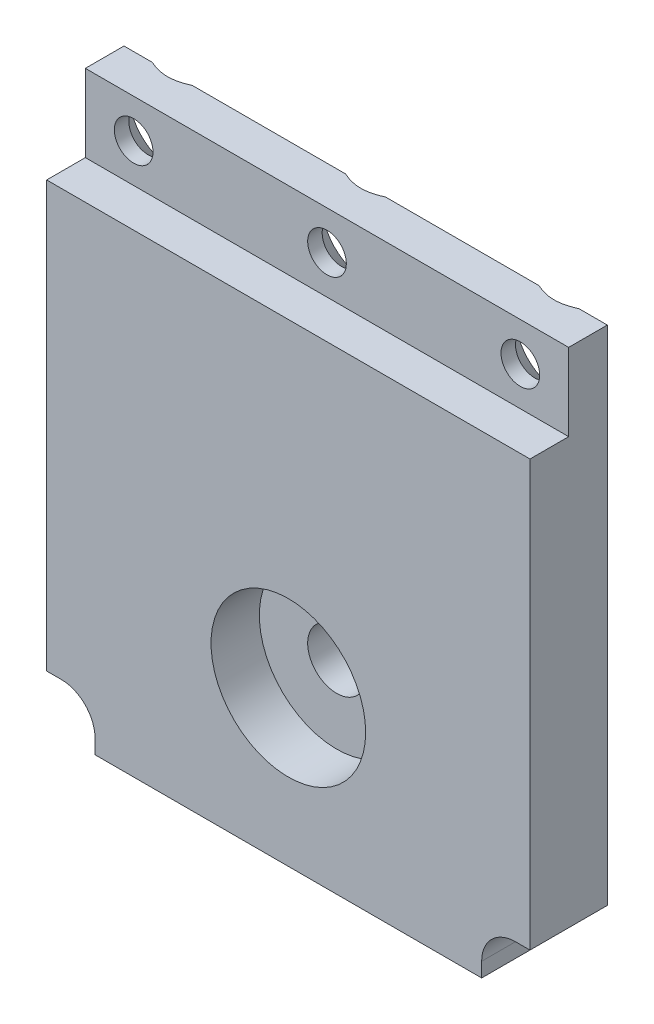
SolidWorks part; units mm, degrees
material "PVC rigide"
ref_plane "Plan de face" through (0, 0, 0) normal (0, 0, 1) x (1, 0, 0)
ref_plane "Plan de dessus" through (0, 0, 0) normal (0, 1, 0) x (1, 0, 0)
ref_plane "Plan de droite" through (0, 0, 0) normal (1, 0, 0) x (0, 0, -1)
sketch "Esquisse1" plane through (0, 0, 0) normal (0, 0, 1) x (1, 0, 0)
  line L0 (-25, -23.5) -> (-20, -23.5)
  line L1 (-25, 28.5) -> (25, 28.5)
  line L2 (-25, 28.5) -> (-25, -23.5)
  line L3 (-20, -28.5) -> (20, -28.5)
  line L4 (25, 28.5) -> (25, -23.5)
  line L5 (-20, -23.5) -> (-20, -28.5)
  line L6 (25, -23.5) -> (20, -23.5)
  line L7 (20, -23.5) -> (20, -28.5)
  line L8 (25, -28.5) -> (25, -23.5) construction
  line L9 (25, -28.5) -> (20, -28.5) construction
  line L10 (-25, -23.5) -> (-25, -28.5) construction
  line L11 (-25, -28.5) -> (-20, -28.5) construction
  line L12 (25, 28.5) -> (-25, -28.5) construction
  line L13 (-25, 28.5) -> (25, -28.5) construction
  point P9 (0, 0)
  dimension "D4" = 5
  dimension "D1" = 50
  dimension "D2" = 57
  dimension "D3" = 5
extrude "Boss.-Extru.1" add sketch "Esquisse1" along normal blind 8
sketch "Esquisse2" plane through (0, -28.5, 0) normal (0, -1, 0) x (1, 0, 0)
  line L0 (-25, 4) -> (25, 4) construction
  line L1 (-25, 8) -> (-25, 0) construction
  line L2 (25, 8) -> (25, 0) construction
  circle A0 centre (-15, 4) radius 2
  circle A1 centre (15, 4) radius 2
  dimension "D1" = 4
  dimension "D2" = 10
  dimension "D3" = 10
extrude "Enlèv. mat.-Extru.1" cut sketch "Esquisse2" against normal blind 10
sketch "Esquisse3" plane through (0, 0, 8) normal (0, 0, 1) x (1, 0, 0)
  line L0 (-25.973, 24.5) -> (39.229, 24.5) construction
  line L1 (25, 28.5) -> (-25, 28.5) construction
  line L2 (-25, 28.5) -> (-25, -23.5) construction
  line L3 (25, -23.5) -> (25, 28.5) construction
  circle A0 centre (-20, 24.5) radius 2
  circle A1 centre (20, 24.5) radius 2
  circle A2 centre (0, 24.5) radius 2
  dimension "D2" = 4
  dimension "D1" = 4
  dimension "D3" = 5
  dimension "D4" = 5
extrude "Enlèv. mat.-Extru.2" cut sketch "Esquisse3" against normal through all
chamfer "Chanfrein1" distance 2.5 angle 45 3 edges at (22, 24.5, 0) (-18, 24.5, 0) (2, 24.5, 0)
sketch "Esquisse4" plane through (0, 0, 8) normal (0, 0, 1) x (1, 0, 0)
  line L0 (-32.372, -12.5) -> (112.9613, -12.5) construction
  line L1 (0, -17.2825) -> (0, 28.5) construction
  line L3 (-20, -28.5) -> (20, -28.5) construction
  line L4 (25, 28.5) -> (-25, 28.5) construction
  circle A0 centre (0, -12.5) radius 8
  point P17 (0, -12.5)
  dimension "D1" = 16
  dimension "D2" = 16
extrude "Enlèv. mat.-Extru.3" cut sketch "Esquisse4" against normal blind 5
sketch "Esquisse5" plane through (0, 0, 3) normal (0, 0, 1) x (1, 0, 0)
  circle A0 centre (0, -12.5) radius 3
  circle A1 centre (0, -12.5) radius 8 construction
  dimension "D1" = 6
extrude "Enlèv. mat.-Extru.4" cut sketch "Esquisse5" against normal through all
sketch "Esquisse6" plane through (0, 0, 8) normal (0, 0, 1) x (1, 0, 0)
  line L0 (25, -23.5) -> (25, 28.5) construction
  line L1 (-25, 28.5) -> (25, 28.5)
  line L2 (-25, 28.5) -> (-25, 20.5)
  line L3 (-25, 20.5) -> (25, 20.5)
  line L5 (25, 20.5) -> (25, 28.5)
  circle A0 centre (-20, 24.5) radius 2 construction
  dimension "D1" = 4
extrude "Enlèv. mat.-Extru.5" cut sketch "Esquisse6" against normal blind 4
fillet "Congé1" radius 3.5 2 edges at (-20, -23.5, 4) (20, -23.5, 4)
